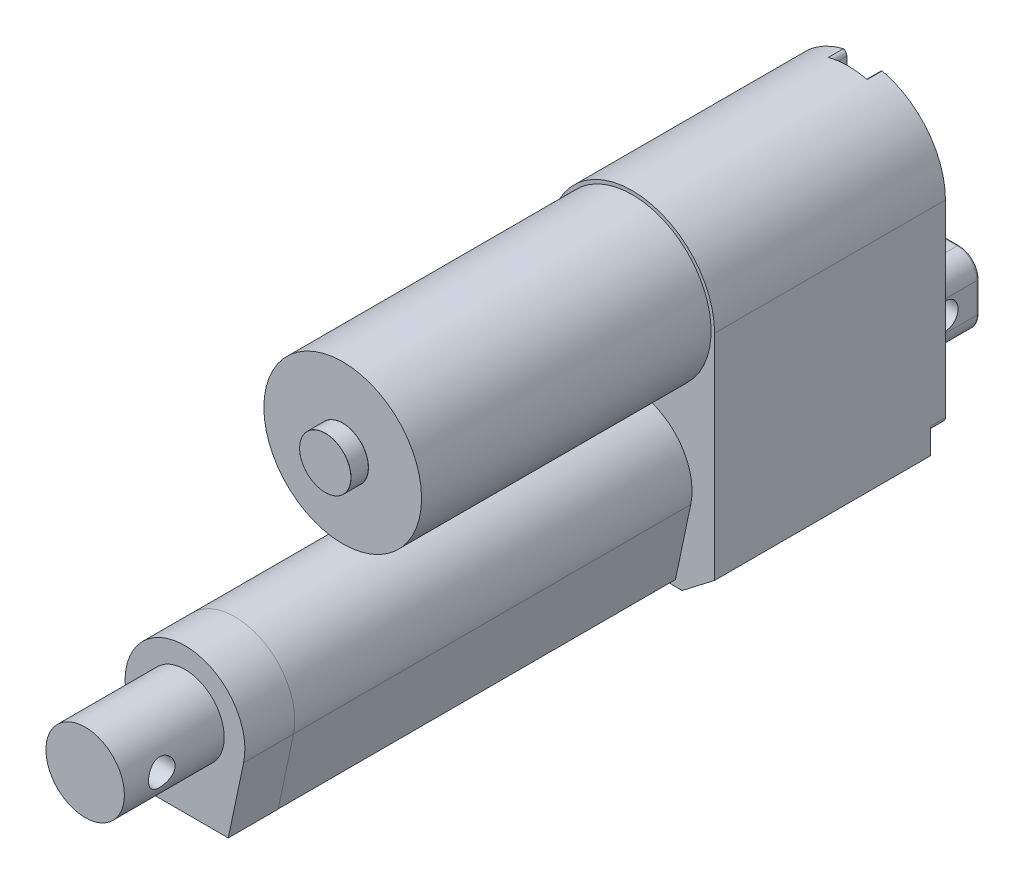
SolidWorks part; units mm, degrees
ref_plane "Front Plane" through (0, 0, 0) normal (0, 0, 1) x (1, 0, 0)
ref_plane "Top Plane" through (0, 0, 0) normal (0, 1, 0) x (1, 0, 0)
ref_plane "Right Plane" through (0, 0, 0) normal (1, 0, 0) x (0, 0, -1)
sketch "Sketch1" plane through (0, 0, 0) normal (0, 0, 1) x (1, 0, 0)
  line L0 (-12.7, 0) -> (12.7, 0)
  line L1 (-20.955, 6.35) -> (-20.955, 60.833)
  line L2 (20.955, 6.35) -> (20.955, 60.833)
  line L3 (12.7, 0) -> (20.955, 6.35)
  line L4 (-20.955, 6.35) -> (-12.7, 0)
  arc A0 (-20.955, 60.833) -> (20.955, 60.833) centre (0, 60.833) cw
  point P0 (0, 81.788)
  dimension "D7" = 81.788
  dimension "D1" = 41.91
  dimension "D2" = 8.255
  dimension "D3" = 12.7
  dimension "D4" = 8.255
  dimension "D5" = 12.7
  dimension "D6" = 6.35
extrude "Boss-Extrude1" add sketch "Sketch1" along normal blind 58.7375
sketch "Sketch2" plane through (0, 0, 58.7375) normal (0, 0, 1) x (1, 0, 0)
  circle A0 centre (0, 60.833) radius 20.066
  arc A1 (20.955, 60.833) -> (-20.955, 60.833) centre (0, 60.833) ccw construction
  dimension "D1" = 40.132
extrude "Boss-Extrude2" add sketch "Sketch2" along normal blind 73.66
sketch "Sketch3" plane through (0, 0, 58.7375) normal (0, 0, 1) x (1, 0, 0)
  line L0 (-12.7, 0) -> (12.7, 0) construction
  line L1 (-14.8881, 20.0427) -> (-10.9969, 1.5621)
  line L2 (-10.9969, 1.5621) -> (10.9969, 1.5621)
  line L3 (10.9969, 1.5621) -> (14.8881, 20.0427)
  line L5 (-10.9969, 1.5621) -> (-10.668, 0) construction
  line L6 (10.9969, 1.5621) -> (10.668, 0) construction
  arc A0 (14.8881, 20.0427) -> (-14.8881, 20.0427) centre (0, 23.1775) ccw
  point P1 (0, 1.5621)
  point P6 (15.2146, 23.1775)
  point P11 (-15.2146, 23.1775)
  point P16 (0, 38.3921)
  dimension "D1" = 23.1775
  dimension "D3" = 36.83
  dimension "D2" = 30.4292
  dimension "D4" = 21.336
extrude "EDIT_LENGTH_HERE (hover for comment)" add sketch "Sketch3" along normal blind 113.792
sketch "Sketch4" plane through (0, 0, 172.5295) normal (0, 0, 1) x (1, 0, 0)
  circle A0 centre (0, 23.1775) radius 9.9822
  arc A1 (14.8881, 20.0427) -> (-14.8881, 20.0427) centre (0, 23.1775) ccw construction
  dimension "D3" = 19.9644
extrude "Boss-Extrude4" add sketch "Sketch4" along normal blind 25.4
sketch "Sketch5" plane through (0, 0, 0) normal (0, 0, -1) x (-1, 0, 0)
  line L0 (12.7, 0) -> (-12.7, 0) construction
  line L1 (-3.81, 32.0675) -> (3.81, 32.0675)
  line L2 (-8.89, 26.9875) -> (-8.89, 19.3675)
  line L3 (-3.81, 14.2875) -> (3.81, 14.2875)
  line L4 (8.89, 26.9875) -> (8.89, 19.3675)
  line L5 (-8.89, 32.0675) -> (8.89, 14.2875) construction
  line L6 (-8.89, 14.2875) -> (8.89, 32.0675) construction
  arc A0 (-8.89, 19.3675) -> (-3.81, 14.2875) centre (-3.81, 19.3675) ccw
  arc A1 (3.81, 14.2875) -> (8.89, 19.3675) centre (3.81, 19.3675) ccw
  arc A2 (3.81, 32.0675) -> (8.89, 26.9875) centre (3.81, 26.9875) cw
  arc A3 (-3.81, 32.0675) -> (-8.89, 26.9875) centre (-3.81, 26.9875) ccw
  point P0 (0, 23.1775)
  dimension "D4" = 5.08
  dimension "D1" = 17.78
  dimension "D2" = 17.78
  dimension "D3" = 14.2875
extrude "Boss-Extrude5" add sketch "Sketch5" along normal blind 20.6502
sketch "Sketch6" plane through (8.89, 0, 0) normal (1, 0, 0) x (0, 0, -1)
  line L0 (11.9062, 14.2875) -> (11.9062, 32.0675) construction
  line L1 (0, 26.9875) -> (0, 19.3675) construction
  line L2 (20.6502, 14.2875) -> (0, 14.2875) construction
  line L3 (-197.9295, 33.1597) -> (-197.9295, 13.1953) construction
  line L4 (20.6502, 32.0675) -> (0, 32.0675) construction
  circle A0 centre (11.9062, 23.1775) radius 3.3782
  circle A1 centre (-188.4045, 23.1775) radius 3.3782
  dimension "D1" = 6.7564
  dimension "D3" = 6.7564
  dimension "D2" = 11.9062
  dimension "D4" = 9.525
extrude "Cut-Extrude3" cut sketch "Sketch6" against normal through all and the other way through all
fillet "Fillet1" radius 2.54 8 edges at (-7.4021, 15.7754, 0) (0, 14.2875, 0) (7.4021, 15.7754, 0) (8.89, 23.1775, 0) (7.4021, 30.5796, 0) (0, 32.0675, 0) (-7.4021, 30.5796, 0) (-8.89, 23.1775, 0)
fillet "Fillet2" radius 0.508 8 edges at (8.89, 23.1775, -20.6502) (7.4021, 30.5796, -20.6502) (0, 32.0675, -20.6502) (-7.4021, 30.5796, -20.6502) (-8.89, 23.1775, -20.6502) (-7.4021, 15.7754, -20.6502) (0, 14.2875, -20.6502) (7.4021, 15.7754, -20.6502)
sketch "Sketch7" plane through (0, 0, 0) normal (0, 0, -1) x (-1, 0, 0)
  line L0 (-4.1275, 77.089) -> (-4.1275, 80.0683)
  line L1 (4.1275, 77.089) -> (4.1275, 79.9786)
  line L2 (-20.955, 6.35) -> (-20.955, 60.833) construction
  line L3 (20.955, 60.833) -> (20.955, 6.35) construction
  line L4 (-13.3956, 1.8544) -> (-11.2223, 6.0477)
  line L5 (-14.605, 11.6109) -> (-19.685, 11.6109)
  line L6 (11.5416, 5.5356) -> (13.4023, 1.8413)
  line L7 (14.605, 11.6109) -> (19.685, 11.6109)
  line L8 (20.955, 6.35) -> (12.7, 0) construction
  line L9 (-12.7, 0) -> (-20.955, 6.35) construction
  line L10 (-20.955, 6.35) -> (-20.955, 12.8809)
  line L11 (12.7, 0) -> (-12.7, 0) construction
  line L12 (-12.7, 0) -> (-20.955, 6.35)
  line L13 (20.955, 12.8809) -> (20.955, 6.35)
  line L14 (20.955, 6.35) -> (12.7, 0)
  arc A0 (-4.1275, 77.089) -> (4.1275, 77.089) centre (0, 77.089) ccw
  arc A1 (20.955, 60.833) -> (-20.955, 60.833) centre (0, 60.833) ccw construction
  arc A2 (6.3689, 80.7967) -> (-6.4572, 80.7683) centre (0, 60.833) ccw
  arc A3 (-6.4572, 80.7683) -> (-4.1275, 80.0683) centre (-5.3975, 80.0683) cw
  arc A4 (4.1275, 79.9786) -> (6.3689, 80.7967) centre (5.3975, 79.9786) cw
  arc A5 (-11.2223, 6.0477) -> (-14.605, 11.6109) centre (-14.605, 7.8009) ccw
  arc A6 (14.605, 11.6109) -> (11.5416, 5.5356) centre (14.605, 7.8009) ccw
  arc A7 (13.4023, 1.8413) -> (12.268, 0) centre (12.268, 1.27) cw
  arc A8 (-13.3956, 1.8544) -> (-12.268, 0) centre (-12.268, 1.27) ccw
  arc A9 (19.685, 11.6109) -> (20.955, 12.8809) centre (19.685, 12.8809) ccw
  arc A10 (-19.685, 11.6109) -> (-20.955, 12.8809) centre (-19.685, 12.8809) cw
  point P12 (4.6513, 81.2653)
  point P39 (20.955, 11.6109)
  point P42 (-20.955, 11.6109)
  line M10 (20.955, 6.35) -> (20.955, 60.833)
  arc M11 (20.955, 60.833) -> (-20.955, 60.833) centre (0, 60.833) ccw
  line M12 (-20.955, 60.833) -> (-20.955, 6.35)
  line M13 (-20.955, 6.35) -> (-12.7, 0)
  dimension "D1" = 8.255
  dimension "D2" = 1.27
  dimension "D3" = 1.27
  dimension "D5" = 7.62
  dimension "D8" = 1.27
  dimension "D9" = 1.27
  dimension "D4" = 16.256
  dimension "D6" = 6.35
  dimension "D7" = 6.35
extrude "Cut-Extrude5" cut sketch "Sketch7" against normal blind 3.81 contours L1 A4 A3 L0 A0 M11 | L5 A10 A8 L4 A5 M12 M13 | A9 L7 A6 L6 A7 L14 M10 region at (15.8698, 7.3642, 0) region at (-15.875, 7.3683, 0) region at (-0.005, 77.7298, 0)
sketch "Sketch8" plane through (0, 0, 132.3975) normal (0, 0, 1) x (1, 0, 0)
  circle A0 centre (0, 60.833) radius 6.5405
  dimension "D1" = 13.081
extrude "Boss-Extrude6" add sketch "Sketch8" along normal blind 4.445
fillet "Fillet3" radius 0.0254 2 edges at (6.5405, 60.833, 132.3975) (6.5405, 60.833, 136.8425)
sketch "Sketch9" plane through (0, 0, 172.5295) normal (0, 0, 1) x (1, 0, 0)
  line L0 (10.9969, 1.5621) -> (14.8881, 20.0427) construction
  line L1 (-14.8881, 20.0427) -> (-10.9969, 1.5621) construction
  line L2 (-10.9969, 1.5621) -> (10.9969, 1.5621) construction
  line L3 (10.9969, 1.5621) -> (14.8881, 20.0427)
  line L4 (-14.8881, 20.0427) -> (-10.9969, 1.5621)
  line L5 (-10.9969, 1.5621) -> (10.9969, 1.5621)
  line L6 (-11.0175, 1.5367) -> (11.0175, 1.5367)
  line L7 (11.0175, 1.5367) -> (14.913, 20.0374)
  line L8 (-14.913, 20.0374) -> (-11.0175, 1.5367)
  arc A0 (14.8881, 20.0427) -> (-14.8881, 20.0427) centre (0, 23.1775) ccw construction
  arc A1 (14.8881, 20.0427) -> (-14.8881, 20.0427) centre (0, 23.1775) ccw
  arc A2 (14.913, 20.0374) -> (-14.913, 20.0374) centre (0, 23.1775) ccw
  dimension "D1" = 0.0254
extrude "Boss-Extrude7" add sketch "Sketch9" against normal blind 12.7
sketch "Sketch10" plane through (0, 0, 3.81) normal (0, 0, -1) x (-1, 0, 0)
  circle A0 centre (0, 77.089) radius 2.54
  circle A1 centre (-14.605, 7.8009) radius 2.54
  circle A2 centre (14.605, 7.8009) radius 2.54
  dimension "D1" = 5.08
extrude "Boss-Extrude8" add sketch "Sketch10" along normal blind 0.635
sketch "Sketch12" plane through (0, 0, 3.175) normal (0, 0, -1) x (-1, 0, 0)
  line L0 (0.3175, 74.3343) -> (0.3175, 75.8444)
  line L1 (-0.2921, 78.359) -> (0.2921, 78.359)
  line L2 (-0.3175, 78.3336) -> (-0.3175, 77.5335)
  line L3 (-0.2921, 75.819) -> (0.2921, 75.819)
  line L4 (0.3175, 78.3336) -> (0.3175, 77.5335)
  line L5 (-0.3175, 78.359) -> (0.3175, 75.819) construction
  line L6 (-0.3175, 75.819) -> (0.3175, 78.359) construction
  line L7 (-1.2446, 77.4065) -> (-0.4445, 77.4065)
  line L8 (-1.27, 77.3811) -> (-1.27, 76.7969)
  line L9 (-1.2446, 76.7715) -> (-0.4445, 76.7715)
  line L10 (1.27, 77.3811) -> (1.27, 76.7763)
  line L11 (-1.27, 77.4065) -> (1.27, 76.7715) construction
  line L12 (-1.27, 76.7715) -> (1.27, 77.4065) construction
  line L13 (0.3264, 74.381) -> (1.2682, 76.767)
  line L14 (-14.2875, 7.3564) -> (-14.2875, 6.5563)
  line L15 (0.4445, 77.4065) -> (1.2446, 77.4065)
  line L16 (-0.3175, 76.6445) -> (-0.3175, 75.8444)
  line L17 (-14.8971, 9.0709) -> (-14.3129, 9.0709)
  line L18 (-14.9225, 9.0455) -> (-14.9225, 8.2454)
  line L19 (-14.8971, 6.5309) -> (-14.3129, 6.5309)
  line L20 (-14.2875, 9.0455) -> (-14.2875, 8.2454)
  line L21 (-14.9225, 9.0709) -> (-14.2875, 6.5309) construction
  line L22 (-14.9225, 6.5309) -> (-14.2875, 9.0709) construction
  line L23 (-15.8496, 8.1184) -> (-15.0495, 8.1184)
  line L24 (-15.875, 8.093) -> (-15.875, 7.5088)
  line L25 (-15.8496, 7.4834) -> (-15.0495, 7.4834)
  line L26 (-13.335, 8.093) -> (-13.335, 7.5088)
  line L27 (-15.875, 8.1184) -> (-13.335, 7.4834) construction
  line L28 (-15.875, 7.4834) -> (-13.335, 8.1184) construction
  line L29 (-14.1605, 7.4834) -> (-13.3604, 7.4834)
  line L30 (-14.1605, 8.1184) -> (-13.3604, 8.1184)
  line L31 (-14.9225, 7.3564) -> (-14.9225, 6.5563)
  line L32 (14.9225, 7.3564) -> (14.9225, 6.5563)
  line L33 (14.3129, 9.0709) -> (14.8971, 9.0709)
  line L34 (14.2875, 9.0455) -> (14.2875, 8.2454)
  line L35 (14.3129, 6.5309) -> (14.8971, 6.5309)
  line L36 (14.9225, 9.0455) -> (14.9225, 8.2454)
  line L37 (14.2875, 9.0709) -> (14.9225, 6.5309) construction
  line L38 (14.2875, 6.5309) -> (14.9225, 9.0709) construction
  line L39 (13.3604, 8.1184) -> (14.1605, 8.1184)
  line L40 (13.335, 8.093) -> (13.335, 7.5088)
  line L41 (13.3604, 7.4834) -> (14.1605, 7.4834)
  line L42 (15.875, 8.093) -> (15.875, 7.5088)
  line L43 (13.335, 8.1184) -> (15.875, 7.4834) construction
  line L44 (13.335, 7.4834) -> (15.875, 8.1184) construction
  line L45 (15.0495, 7.4834) -> (15.8496, 7.4834)
  line L46 (15.0495, 8.1184) -> (15.8496, 8.1184)
  line L47 (14.2875, 7.3564) -> (14.2875, 6.5055)
  arc A0 (-0.4445, 76.7715) -> (-0.3175, 76.6445) centre (-0.4445, 76.6445) cw
  arc A1 (0.3264, 74.381) -> (0.3175, 74.3343) centre (0.4445, 74.3343) ccw
  arc A2 (0.3175, 77.5335) -> (0.4445, 77.4065) centre (0.4445, 77.5335) ccw
  arc A3 (-0.4445, 77.4065) -> (-0.3175, 77.5335) centre (-0.4445, 77.5335) ccw
  arc A4 (-1.2446, 77.4065) -> (-1.27, 77.3811) centre (-1.2446, 77.3811) ccw
  arc A5 (-1.27, 76.7969) -> (-1.2446, 76.7715) centre (-1.2446, 76.7969) ccw
  arc A6 (-0.3175, 75.8444) -> (-0.2921, 75.819) centre (-0.2921, 75.8444) ccw
  arc A7 (0.2921, 75.819) -> (0.3175, 75.8444) centre (0.2921, 75.8444) ccw
  arc A8 (1.2682, 76.767) -> (1.27, 76.7763) centre (1.2446, 76.7763) ccw
  arc A9 (1.2446, 77.4065) -> (1.27, 77.3811) centre (1.2446, 77.3811) cw
  arc A10 (0.2921, 78.359) -> (0.3175, 78.3336) centre (0.2921, 78.3336) cw
  arc A11 (-0.2921, 78.359) -> (-0.3175, 78.3336) centre (-0.2921, 78.3336) ccw
  arc A12 (-15.0495, 7.4834) -> (-14.9225, 7.3564) centre (-15.0495, 7.3564) cw
  arc A13 (-14.1605, 7.4834) -> (-14.2875, 7.3564) centre (-14.1605, 7.3564) ccw
  arc A14 (-14.2875, 8.2454) -> (-14.1605, 8.1184) centre (-14.1605, 8.2454) ccw
  arc A15 (-15.0495, 8.1184) -> (-14.9225, 8.2454) centre (-15.0495, 8.2454) ccw
  arc A16 (-15.8496, 8.1184) -> (-15.875, 8.093) centre (-15.8496, 8.093) ccw
  arc A17 (-15.875, 7.5088) -> (-15.8496, 7.4834) centre (-15.8496, 7.5088) ccw
  arc A18 (-14.9225, 6.5563) -> (-14.8971, 6.5309) centre (-14.8971, 6.5563) ccw
  arc A19 (-14.3129, 6.5309) -> (-14.2875, 6.5563) centre (-14.3129, 6.5563) ccw
  arc A20 (-13.3604, 7.4834) -> (-13.335, 7.5088) centre (-13.3604, 7.5088) ccw
  arc A21 (-13.3604, 8.1184) -> (-13.335, 8.093) centre (-13.3604, 8.093) cw
  arc A22 (-14.3129, 9.0709) -> (-14.2875, 9.0455) centre (-14.3129, 9.0455) cw
  arc A23 (-14.8971, 9.0709) -> (-14.9225, 9.0455) centre (-14.8971, 9.0455) ccw
  arc A26 (14.1605, 7.4834) -> (14.2875, 7.3564) centre (14.1605, 7.3564) cw
  arc A27 (15.0495, 7.4834) -> (14.9225, 7.3564) centre (15.0495, 7.3564) ccw
  arc A28 (14.9225, 8.2454) -> (15.0495, 8.1184) centre (15.0495, 8.2454) ccw
  arc A29 (14.1605, 8.1184) -> (14.2875, 8.2454) centre (14.1605, 8.2454) ccw
  arc A30 (13.3604, 8.1184) -> (13.335, 8.093) centre (13.3604, 8.093) ccw
  arc A31 (13.335, 7.5088) -> (13.3604, 7.4834) centre (13.3604, 7.5088) ccw
  arc A32 (14.2875, 6.5055) -> (14.3129, 6.5309) centre (14.3129, 6.5055) ccw
  arc A33 (14.8971, 6.5309) -> (14.9225, 6.5563) centre (14.8971, 6.5563) ccw
  arc A34 (15.8496, 7.4834) -> (15.875, 7.5088) centre (15.8496, 7.5088) ccw
  arc A35 (15.8496, 8.1184) -> (15.875, 8.093) centre (15.8496, 8.093) cw
  arc A36 (14.8971, 9.0709) -> (14.9225, 9.0455) centre (14.8971, 9.0455) cw
  arc A37 (14.3129, 9.0709) -> (14.2875, 9.0455) centre (14.3129, 9.0455) ccw
  point P0 (0, 77.089)
  point P6 (0, 77.089)
  point P16 (-0.3175, 76.7715)
  point P20 (0.3175, 74.3585)
  point P23 (0.3175, 77.4065)
  point P50 (-14.605, 7.8009)
  point P55 (-14.605, 7.8009)
  point P96 (14.605, 7.8009)
  point P101 (14.605, 7.8009)
  dimension "D5" = 0.127
  dimension "D6" = 0.0254
  dimension "D11" = 0.127
  dimension "D12" = 0.0254
  dimension "D17" = 0.127
  dimension "D18" = 0.0254
  dimension "D1" = 0.635
  dimension "D2" = 2.54
  dimension "D3" = 0.635
  dimension "D4" = 2.54
  dimension "D7" = 0.635
  dimension "D8" = 2.54
  dimension "D9" = 0.635
  dimension "D10" = 2.54
  dimension "D13" = 0.635
  dimension "D14" = 2.54
  dimension "D15" = 0.635
  dimension "D16" = 2.54
dome "Dome1" [suppressed] faces to dome 3 distance 1.27 parameters "D1"=1.27
extrude "Cut-Extrude7" [suppressed] cut sketch "Sketch12" along normal up to next
